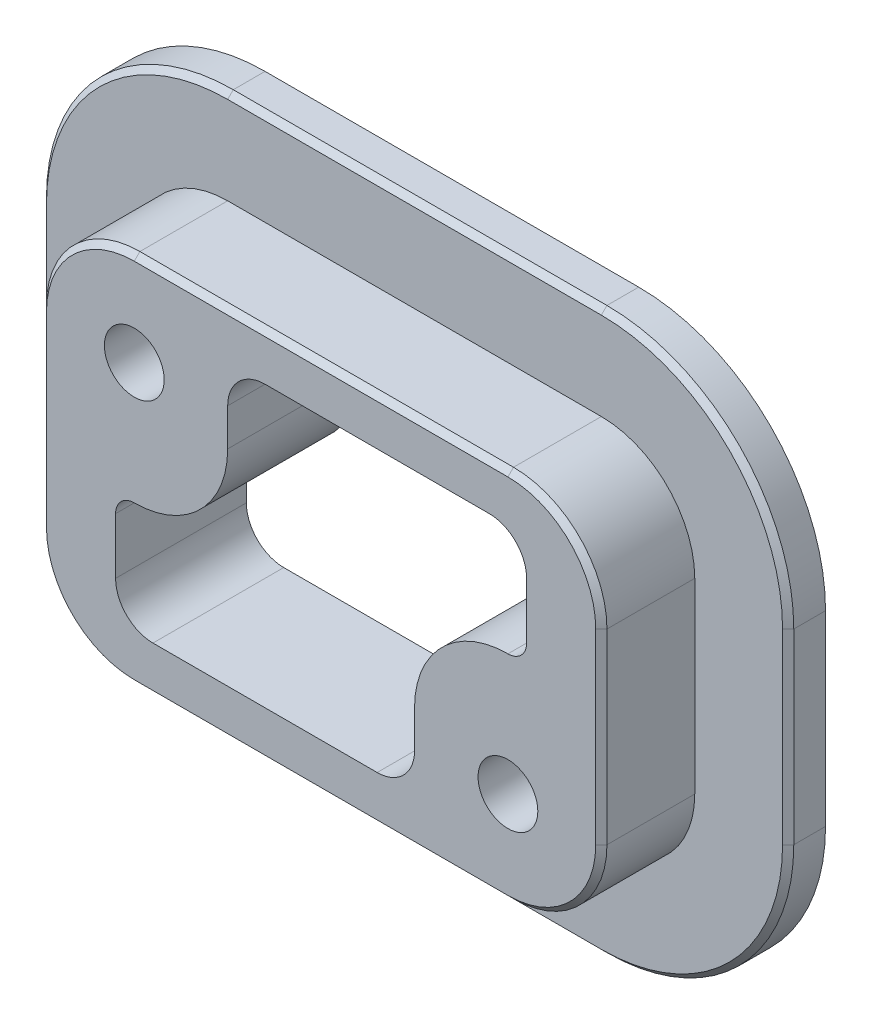
SolidWorks part; units mm, degrees
ref_plane "Ebene vorne" through (0, 0, 0) normal (0, 0, 1) x (1, 0, 0)
ref_plane "Ebene oben" through (0, 0, 0) normal (0, 1, 0) x (1, 0, 0)
ref_plane "Ebene rechts" through (0, 0, 0) normal (1, 0, 0) x (0, 0, -1)
sketch "Skizze1" plane through (0, 0, 0) normal (0, 0, 1) x (1, 0, 0)
  line L1 (15, 10) -> (-15, 10)
  line L2 (15, 10) -> (15, -10)
  line L3 (15, -10) -> (-15, -10)
  line L4 (-15, 10) -> (-15, -10)
  line L5 (15, 10) -> (-15, -10) construction
  line L6 (15, -10) -> (-15, 10) construction
  point P0 (0, 0)
  dimension "D1" = 20
  dimension "D2" = 30
extrude "Aufsatz-Linear austragen1" add sketch "Skizze1" along normal blind 5
fillet "Verrundung1" radius 5 4 edges at (-15, 10, 2.5) (-15, -10, 2.5) (15, -10, 2.5) (15, 10, 2.5)
sketch "Skizze2" plane through (0, 0, 0) normal (0, 0, -1) x (-1, 0, 0)
  line L8 (20, -5) -> (20, 5)
  line L9 (10, 15) -> (-10, 15)
  line L10 (-20, 5) -> (-20, -5)
  line L11 (-10, -15) -> (10, -15)
  line L12 (20, -5) -> (20, 5)
  line L13 (10, 15) -> (-10, 15)
  line L14 (-20, 5) -> (-20, -5)
  line L15 (-10, -15) -> (10, -15)
  arc A8 (20, 5) -> (10, 15) centre (10, 5) ccw
  arc A9 (-10, 15) -> (-20, 5) centre (-10, 5) ccw
  arc A10 (-20, -5) -> (-10, -15) centre (-10, -5) ccw
  arc A11 (10, -15) -> (20, -5) centre (10, -5) ccw
  arc A12 (20, 5) -> (10, 15) centre (10, 5) ccw
  arc A13 (-10, 15) -> (-20, 5) centre (-10, 5) ccw
  arc A14 (-20, -5) -> (-10, -15) centre (-10, -5) ccw
  arc A15 (10, -15) -> (20, -5) centre (10, -5) ccw
  dimension "D1" = 5
extrude "Aufsatz-Linear austragen2" add sketch "Skizze2" along normal blind 2
sketch "Skizze3" plane through (0, 0, 5) normal (0, 0, 1) x (1, 0, 0)
  circle A0 centre (-10, 5) radius 1.6
  circle A1 centre (10, -5) radius 1.6
  dimension "D1" = 3.2
extrude "Schnitt-Linear austragen1" cut sketch "Skizze3" against normal through all
sketch "Skizze4" plane through (0, 0, -2) normal (0, 0, -1) x (-1, 0, 0)
  line L1 (10, 8.4641) -> (7, 6.7321)
  line L2 (7, 6.7321) -> (7, 3.2679)
  line L3 (7, 3.2679) -> (10, 1.5359)
  line L4 (10, 1.5359) -> (13, 3.2679)
  line L5 (13, 3.2679) -> (13, 6.7321)
  line L6 (13, 6.7321) -> (10, 8.4641)
  line L7 (-10, -1.5359) -> (-13, -3.2679)
  line L8 (-13, -3.2679) -> (-13, -6.7321)
  line L9 (-13, -6.7321) -> (-10, -8.4641)
  line L10 (-10, -8.4641) -> (-7, -6.7321)
  line L11 (-7, -6.7321) -> (-7, -3.2679)
  line L12 (-7, -3.2679) -> (-10, -1.5359)
  circle A0 centre (10, 5) radius 3 construction
  circle A1 centre (-10, -5) radius 3 construction
  point P9 (10, 5)
  dimension "D1" = 6
extrude "Schnitt-Linear austragen2" cut sketch "Skizze4" against normal blind 3
sketch "Skizze5" plane through (0, 0, 5) normal (0, 0, 1) x (1, 0, 0)
  line L1 (5, 7.5) -> (-5, 7.5)
  line L2 (5, 1.5) -> (5, -7.5)
  line L3 (5, -7.5) -> (-5, -7.5)
  line L4 (-5, 7.5) -> (-5, -1.5)
  line L5 (5, 7.5) -> (-5, -7.5) construction
  line L6 (5, -7.5) -> (-5, 7.5) construction
  line L7 (-5, -7.5) -> (-11, -7.5)
  line L9 (-5, -1.5) -> (-11, -1.5)
  line L10 (-11, -7.5) -> (-11, -1.5)
  line L11 (5, 7.5) -> (11, 7.5)
  line L13 (5, 1.5) -> (11, 1.5)
  line L14 (11, 7.5) -> (11, 1.5)
  point P0 (0, 0)
  dimension "D1" = 15
  dimension "D2" = 10
  dimension "D3" = 6
  dimension "D4" = 6
extrude "Schnitt-Linear austragen3" cut sketch "Skizze5" against normal through all
fillet "Verrundung2" radius 5 2 edges at (5, 1.5, 1.5) (-5, -1.5, 1.5)
fillet "Verrundung3" radius 2 4 edges at (5, -7.5, 1.5) (-11, -7.5, 1.5) (-5, 7.5, 1.5) (11, 7.5, 1.5)
fillet "Verrundung4" radius 1 2 edges at (11, 1.5, 1.5) (-11, -1.5, 1.5)
chamfer "Fase1" distance 0.3 angle 45 16 edges at (0, -15, 0) (-17.0711, -12.0711, 0) (17.0711, -12.0711, 0) (-20, 0, 0) (20, 0, 0) (-17.0711, 12.0711, 0) (17.0711, 12.0711, 0) (0, 15, 0) (0, -10, 5) (13.5355, -8.5355, 5) (-13.5355, -8.5355, 5) (15, 0, 5) (-15, 0, 5) (13.5355, 8.5355, 5) (-13.5355, 8.5355, 5) (0, 10, 5)
